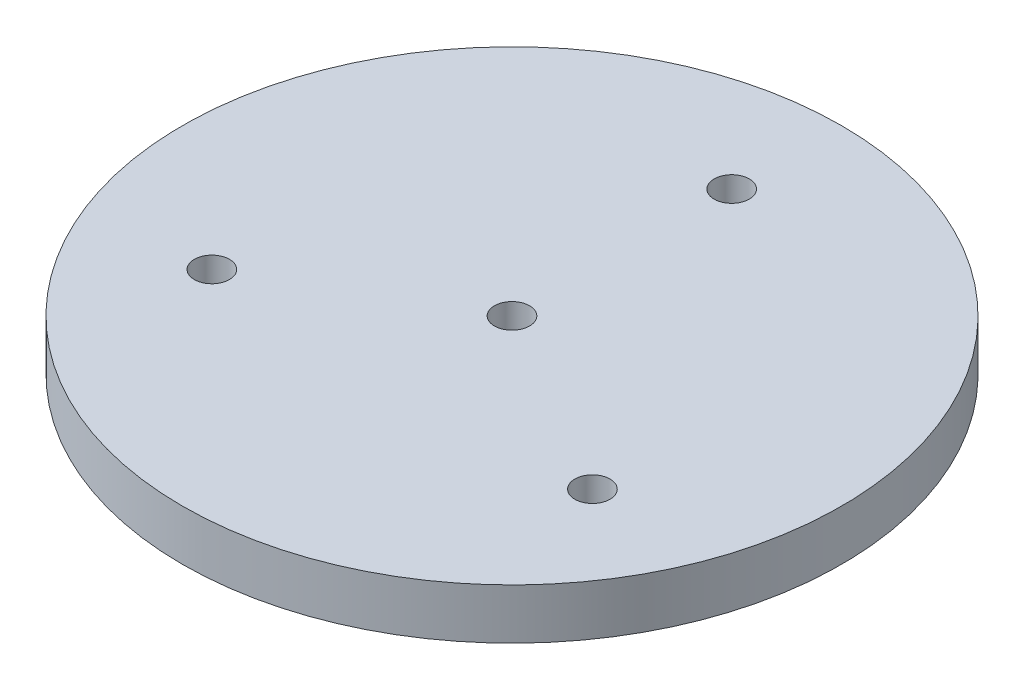
SolidWorks part; units mm, degrees
material "Zoltek Panex 33"
ref_plane "Ebene vorne" through (0, 0, 0) normal (0, 0, 1) x (1, 0, 0)
ref_plane "Ebene oben" through (0, 0, 0) normal (0, 1, 0) x (1, 0, 0)
ref_plane "Ebene rechts" through (0, 0, 0) normal (1, 0, 0) x (0, 0, -1)
sketch "Sketch1" plane through (0, 0, 0) normal (0, 1, 0) x (1, 0, 0)
  circle A0 centre (0, 0) radius 75
  dimension "D1" = 150
extrude "Boss-Extrude1" add sketch "Sketch1" along normal blind 11.482
sketch "Sketch2" plane through (0, 11.482, 0) normal (0, 1, 0) x (1, 0, 0)
  circle A0 centre (0, 50) radius 4
  dimension "D1" = 8
  dimension "D2" = 50
extrude "Cut-Extrude1" cut sketch "Sketch2" against normal through all contours A0
ref_axis "Axis1" through (0, 12.0561, 0) along (0, -1, 0)
pattern_circular "CirPattern1" count 3 over 360 about axis through (0, 12.0561, 0) along (0, -1, 0) of "Cut-Extrude1"
sketch "Sketch3" plane through (0, 11.482, 0) normal (0, 1, 0) x (1, 0, 0)
  circle A0 centre (0, 0) radius 4
  dimension "D1" = 8
extrude "Cut-Extrude2" cut sketch "Sketch3" against normal through all
equation "\"d_i_tube\"= 150mm'Inner Rocket Body Composite Tube Diameter"
equation "\"t_tube\"= 1.182mm'Thickness of Rocket Body Composite Tube"
equation "\"l_upper_body_tube\"= 949.3mm'Upper Rocket Body Composite Tube length"
equation "\"l_lower_body_tube\"= 816mm'Lower Rocket Body Composite Tube Length"
equation "\"d_a_NC\"= 154mm'Outer Diameter of Nosecone base"
equation "\"d_i_phenolic_tube\"= 152.3mm'Inner Phenolic Tube Diameter"
equation "\"t_phenolic_tube\"= 2mm'Thickness of Phenolic Body Tube"
equation "\"l_fin_cut\"= 220mm'Length of fin on Motor Retainer"
equation "\"t_SW-Panel\"= 11.482mm'Thickness of Sandwich-Panel"
equation "\"l_motor_tube\"=610mm'Length of phenolic motor tube"
equation "\"d_i_motor_tube\"=99.06mm'Inner diameter of phenolic motor tube"
equation "\"t_motor_tube\"=1.58mm'Thicknes of phenolic motor tube"
equation "\"l_cut_fin_centering\"=13mm'Length of cut for fin alignement on fin centering rings"
equation "\"l_M3_threaded_rods\"=220mm'Length of M3 threaded rods for thrust plate force transmission"
equation "\"D1@Boss-Extrude1\"=\"t_SW-Panel\""
equation "\"D1@Sketch1\"=\"d_i_tube\""
